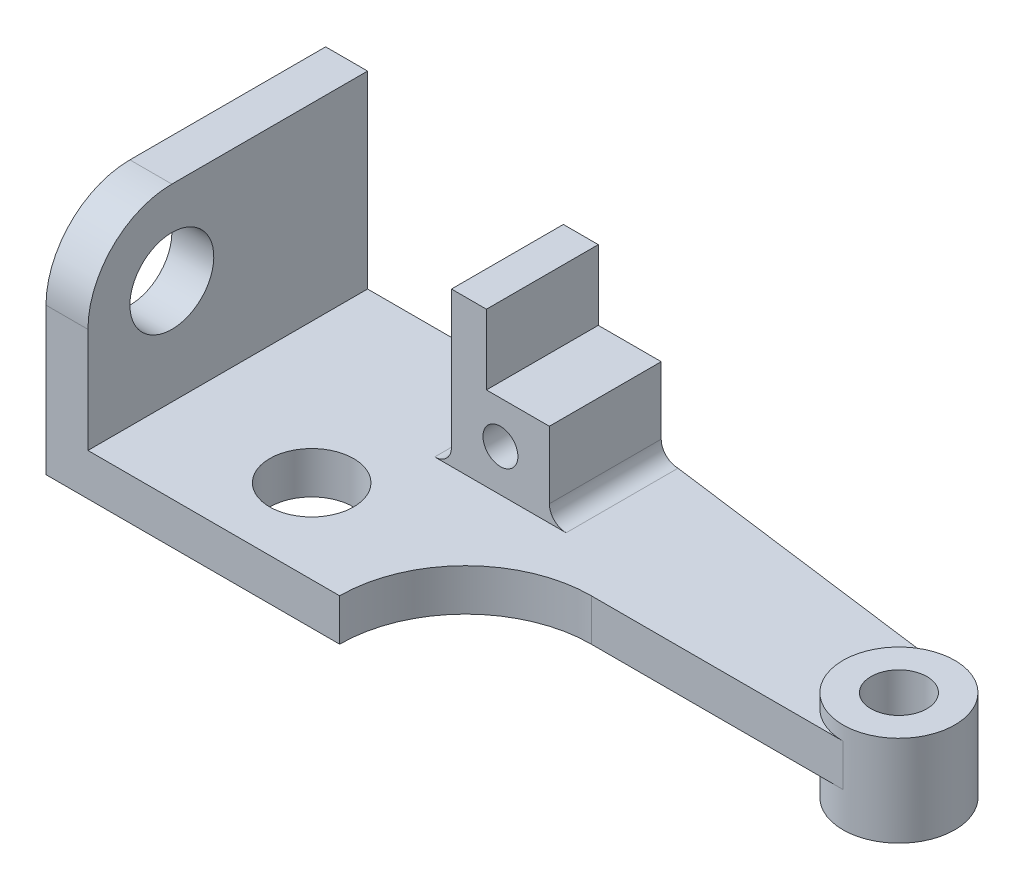
SolidWorks part; units mm, degrees
ref_plane "Front Plane" through (0, 0, 0) normal (0, 0, 1) x (1, 0, 0)
ref_plane "Top Plane" through (0, 0, 0) normal (0, 1, 0) x (1, 0, 0)
ref_plane "Right Plane" through (0, 0, 0) normal (1, 0, 0) x (0, 0, -1)
sketch "Sketch1" plane through (0, 0, 0) normal (0, 0, 1) x (1, 0, 0)
  line L0 (152.4, 12.7) -> (152.4, 9.525) construction
  line L1 (0, 0) -> (92.075, 0)
  line L2 (0, 0) -> (0, 9.525)
  line L3 (9.525, 9.525) -> (50.165, 9.525)
  line L4 (165.1, 0) -> (165.1, 9.525)
  line L5 (165.1, 12.7) -> (139.7, 12.7)
  line L6 (165.1, 12.7) -> (165.1, -7.9375)
  line L7 (165.1, -7.9375) -> (139.7, -7.9375)
  line L8 (139.7, 12.7) -> (139.7, -7.9375)
  line L9 (152.4, 0) -> (152.4, -7.9375) construction
  line L10 (127, 0) -> (165.1, 0)
  line L12 (76.2, 13.335) -> (76.2, 28.575)
  line L13 (76.2, 28.575) -> (61.9125, 28.575)
  line L14 (53.975, 13.335) -> (53.975, 28.575)
  line L15 (92.075, 0) -> (127, 0)
  line L16 (53.975, 28.575) -> (53.975, 44.45)
  line L17 (53.975, 44.45) -> (61.9125, 44.45)
  line L18 (61.9125, 28.575) -> (61.9125, 44.45)
  line L19 (0, 9.525) -> (9.525, 9.525)
  line L20 (0, 9.525) -> (0, 52.3875)
  line L21 (0, 52.3875) -> (9.525, 52.3875)
  line L22 (9.525, 9.525) -> (9.525, 52.3875)
  line L23 (120.65, -6.35) -> (120.65, -12.7)
  line L25 (98.425, -6.35) -> (98.425, -12.7)
  line L26 (80.01, 9.525) -> (165.1, 9.525)
  line L27 (50.165, 9.525) -> (80.01, 9.525)
  circle A0 centre (65.0875, 19.05) radius 3.9687
  arc A1 (98.425, -12.7) -> (120.65, -12.7) centre (109.5375, -12.7) ccw
  circle A2 centre (109.5375, -12.7) radius 3.9688
  arc A3 (92.075, 0) -> (98.425, -6.35) centre (92.075, -6.35) cw
  arc A4 (127, 0) -> (120.65, -6.35) centre (127, -6.35) ccw
  arc A6 (80.01, 9.525) -> (76.2, 13.335) centre (80.01, 13.335) cw
  arc A7 (50.165, 9.525) -> (53.975, 13.335) centre (50.165, 13.335) ccw
  point P35 (120.65, 0)
  point P42 (76.2, 9.525)
  dimension "D13" = 7.9375
  dimension "D16" = 22.225
  dimension "D19" = 6.35
  dimension "D20" = 6.35
  dimension "D28" = 3.81
  dimension "D3" = 20.6375
  dimension "D4" = 25.4
  dimension "D5" = 42.8625
  dimension "D6" = 9.525
  dimension "D7" = 52.3875
  dimension "D8" = 14.2875
  dimension "D9" = 22.225
  dimension "D10" = 34.925
  dimension "D11" = 19.05
  dimension "D12" = 9.525
  dimension "D14" = 3.175
  dimension "D15" = 44.45
  dimension "D17" = 12.7
  dimension "D18" = 22.225
  dimension "D21" = 3.175
  dimension "D24" = 142.875
  dimension "D25" = 9.525
extrude "Boss-Extrude1" add sketch "Sketch1" along normal blind 9.525 contours L3 L22 L21 L20 | A4 L10 L8 L3 L2 L1 A3 L25 A1 L23 A2 | L13 L18 L17 L16 L14 L3 L12 A0 | L8 L10 L4 L3 | L5 L8 L3 L6 | L10 L8 L7 L6 | A4 L15 A3 L25 A1 L23 A2 | L22 L19 L2 L1 L15 L10 L8 L26 L27 L3 region at (69.85, 4.7625, 0) region at (109.5375, -0.4227, 0) region at (4.7625, 30.9562, 0) region at (152.4, -3.9688, 0) region at (152.4, 4.7625, 0) region at (63.309, 23.2907, 0) region at (152.4, 11.1125, 0)
extrude "Boss-Extrude4" add sketch "Sketch1<7>" along normal blind 25.4 contours L22 L19 L2 L1 L15 L10 L8 L26 L27 L3 | A7 L27 A6 L12 L13 L18 L17 L16 L14 A0 | L26 L8 L10 L4 | L10 L8 L7 L6 | L8 L26 L6 L5 | L20 L21 L22 L19 region at (69.85, 4.7625, 0) region at (152.4, -3.9688, 0) region at (152.4, 4.7625, 0) region at (63.309, 23.2907, 0) region at (152.4, 11.1125, 0)
sketch "Sketch1<7>" plane through (0, 0, 0) normal (0, 0, 1) x (1, 0, 0) same geometry as "Sketch1"
extrude "Boss-Extrude5" add sketch "Sketch1<8>" along normal blind 63.5 contours L22 L19 L2 L1 L15 L10 L8 L26 L27 L3 | L26 L8 L10 L4 | L8 L26 L6 L5 | L10 L8 L7 L6 | L19 L22 L21 L20 region at (69.85, 4.7625, 0) region at (4.7625, 30.9562, 0) region at (152.4, -3.9688, 0) region at (152.4, 4.7625, 0) region at (152.4, 11.1125, 0)
sketch "Sketch1<8>" plane through (0, 0, 0) normal (0, 0, 1) x (1, 0, 0) same geometry as "Sketch1"
sketch "Sketch4" plane through (9.525, 0, 0) normal (1, 0, 0) x (0, 0, -1)
  line L0 (-63.5, 9.525) -> (0, 9.525) construction
  line L1 (-63.5, 33.3375) -> (-63.5, 9.525)
  line L2 (-44.45, 52.3875) -> (0, 52.3875)
  circle A0 centre (-44.45, 33.3375) radius 9.525
  arc A1 (-63.5, 33.3375) -> (-44.45, 52.3875) centre (-44.45, 33.3375) cw
  point P12 (-63.5, 52.3875)
  line M2 (0, 52.3875) -> (-63.5, 52.3875)
  line M3 (-63.5, 52.3875) -> (-63.5, 9.525)
  dimension "D2" = 19.05
  dimension "D3" = 19.05
  dimension "D1" = 23.8125
extrude "Cut-Extrude1" cut sketch "Sketch4" against normal through all contours A1 M3 M2 | A0 region at (9.525, 33.3375, 44.45) region at (9.525, 48.1323, 59.2448)
sketch "Sketch2" plane through (0, 12.7, 0) normal (0, 1, 0) x (1, 0, 0)
  line L0 (165.1, 0) -> (139.7, 0) construction
  line L1 (152.4, 0) -> (152.4, -63.5) construction
  line L2 (165.1, -63.5) -> (139.7, -63.5) construction
  line L3 (152.4, -9.525) -> (80.01, 0)
  line L4 (80.01, 0) -> (165.1, 0)
  line L5 (165.1, 0) -> (165.1, -22.225)
  line L6 (165.1, -63.5) -> (165.1, 0) construction
  line L7 (9.525, -63.5) -> (139.7, -63.5) construction
  line L9 (152.4, -34.925) -> (95.25, -34.925)
  line L10 (66.675, -63.5) -> (165.1, -63.5)
  line L11 (165.1, -63.5) -> (165.1, -22.225)
  line L13 (9.525, -63.5) -> (9.525, 0) construction
  line L15 (139.7, -34.925) -> (139.7, -7.8539)
  line L16 (139.7, -63.5) -> (139.7, 0) construction
  circle A0 centre (152.4, -22.225) radius 12.7
  circle A1 centre (152.4, -22.225) radius 6.35
  circle A2 centre (95.25, -63.5) radius 28.575
  circle A3 centre (41.275, -44.45) radius 9.525
  line M5 (139.7, 0) -> (139.7, -63.5)
  line M6 (139.7, -63.5) -> (165.1, -63.5)
  line M7 (165.1, -63.5) -> (165.1, 0)
  line M8 (165.1, 0) -> (139.7, 0)
  dimension "D1" = 25.4
  dimension "D2" = 12.7
  dimension "D4" = 57.15
  dimension "D5" = 66.675
  dimension "D6" = 19.05
  dimension "D3" = 22.225
  dimension "D7" = 31.75
extrude "Cut-Extrude2" cut sketch "Sketch2" against normal through all contours A3 | L10 A2 | A2 L10 L9 M5 | A0 L1 L10 M7 | L1 L9 M5 M6 | L1 A0 M8 M7 | L1 L4 L3 M5 | L4 L3 M5 | L1 A1 | A1 L1 region at (159.5316, 12.7, 6.4532) region at (146.2535, 12.7, 4.3581) region at (119.8033, 12.7, 2.618) region at (155.095, 12.7, 22.225) region at (149.705, 12.7, 22.225) region at (159.0559, 12.7, 47.7214) region at (146.05, 12.7, 49.2125) region at (127.7722, 12.7, 47.0099) region at (95.25, 12.7, 51.3724) region at (41.275, 12.7, 44.45)
extrude "Cut-Extrude3" cut sketch "Sketch2<3>" against normal up to surface (3.175 mm away) contours A0 L9 M5 | A0 L3 M5 region at (142.8645, 12.7, 11.5655) region at (142.5368, 12.7, 32.0882) up to face at (41.275, 9.525, 53.975)
sketch "Sketch2<3>" plane through (0, 12.7, 0) normal (0, 1, 0) x (1, 0, 0) same geometry as "Sketch2"
extrude "Cut-Extrude4" cut sketch "Sketch2<5>" along normal up to surface (-12.7 mm away) from vertex contours A0 L3 M5 | A0 L15 L9 region at (142.8645, 12.7, 11.5655) region at (142.5368, 12.7, 32.0882) up to face at (41.275, 0, 53.975) starting at point (139.7, -7.9375, 7.8539)
sketch "Sketch2<5>" plane through (0, 12.7, 0) normal (0, 1, 0) x (1, 0, 0) same geometry as "Sketch2"
